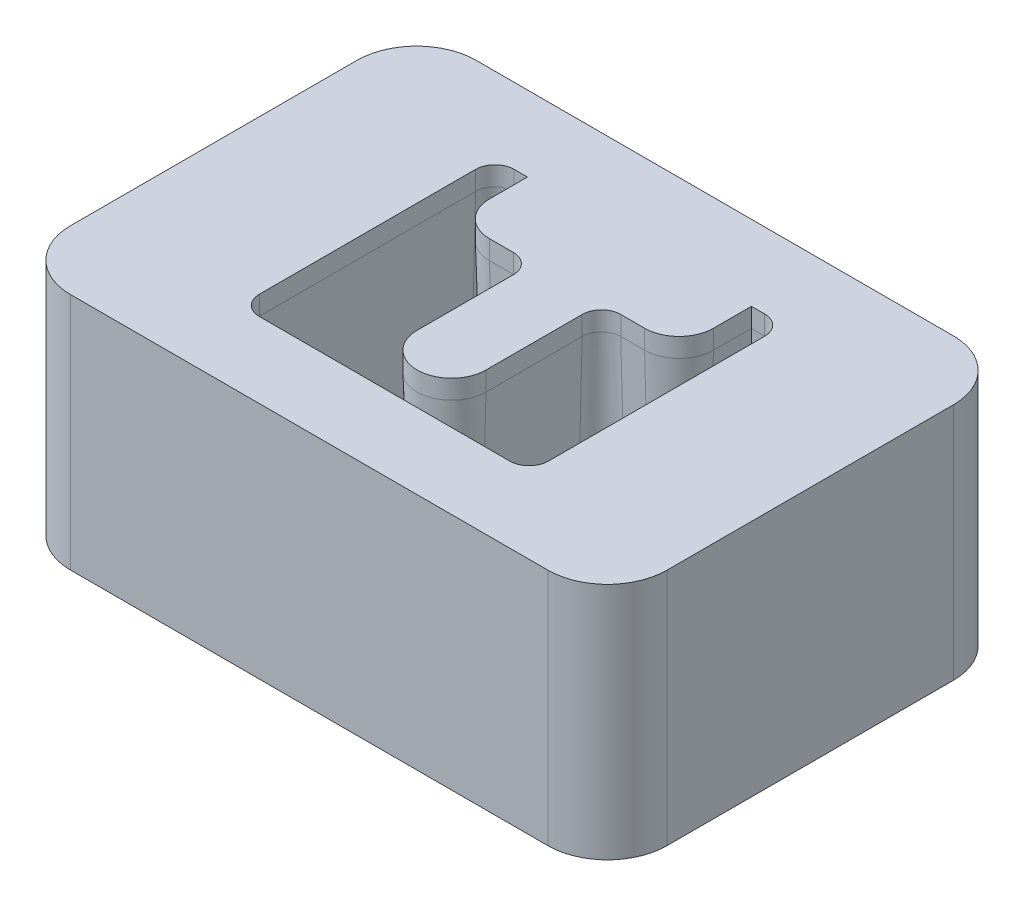
SolidWorks part; units mm, degrees
material "K110"
ref_plane "Front Plane" through (0, 0, 0) normal (0, 0, 1) x (1, 0, 0)
ref_plane "Top Plane" through (0, 0, 0) normal (0, 1, 0) x (1, 0, 0)
ref_plane "Right Plane" through (0, 0, 0) normal (1, 0, 0) x (0, 0, -1)
sketch "Sketch1" plane through (0, 0, 0) normal (0, 1, 0) x (1, 0, 0)
  line L1 (-50, -34) -> (50, -34)
  line L2 (-50, -34) -> (-50, 34)
  line L3 (-50, 34) -> (50, 34)
  line L4 (50, -34) -> (50, 34)
  line L5 (-50, -34) -> (50, 34) construction
  line L6 (-50, 34) -> (50, -34) construction
  point P0 (0, 0)
  dimension "D1" = 68
  dimension "D2" = 100
extrude "Boss-Extrude1" add sketch "Sketch1" against normal blind 40
fillet "Fillet1" radius 10 4 edges at (-50, -20, -34) (50, -20, -34) (50, -20, 34) (-50, -20, 34)
sketch "Sketch2" plane through (0, 0, 0) normal (0, 1, 0) x (1, 0, 0)
  line L22 (-21, -21.36) -> (21, -21.36)
  line L23 (-24.23, 18.13) -> (-24.23, -18.13)
  line L24 (-18.77, 21.36) -> (-21, 21.36)
  line L25 (-18.77, 15) -> (-18.77, 21.36)
  line L26 (-9, 9.23) -> (-13, 9.23)
  line L27 (-5.77, -10.13) -> (-5.77, 6)
  line L28 (5.77, 6) -> (5.77, -10.13)
  line L29 (13, 9.23) -> (9, 9.23)
  line L30 (18.77, 21.36) -> (18.77, 15)
  line L31 (21, 21.36) -> (18.77, 21.36)
  line L32 (24.23, -18.13) -> (24.23, 18.13)
  line L33 (-21, -21.36) -> (21, -21.36)
  line L34 (-24.23, 18.13) -> (-24.23, -18.13)
  line L35 (-18.77, 21.36) -> (-21, 21.36)
  line L36 (-18.77, 15) -> (-18.77, 21.36)
  line L37 (-9, 9.23) -> (-13, 9.23)
  line L38 (-5.77, -10.13) -> (-5.77, 6)
  line L39 (5.77, 6) -> (5.77, -10.13)
  line L40 (13, 9.23) -> (9, 9.23)
  line L41 (18.77, 21.36) -> (18.77, 15)
  line L42 (21, 21.36) -> (18.77, 21.36)
  line L43 (24.23, -18.13) -> (24.23, 18.13)
  arc A18 (21, -21.36) -> (24.23, -18.13) centre (21, -18.13) ccw
  arc A19 (-24.23, -18.13) -> (-21, -21.36) centre (-21, -18.13) ccw
  arc A20 (-21, 21.36) -> (-24.23, 18.13) centre (-21, 18.13) ccw
  arc A21 (-18.77, 15) -> (-13, 9.23) centre (-13, 15) ccw
  arc A22 (-5.77, 6) -> (-9, 9.23) centre (-9, 6) ccw
  arc A23 (-5.77, -10.13) -> (5.77, -10.13) centre (0, -10.13) ccw
  arc A24 (9, 9.23) -> (5.77, 6) centre (9, 6) ccw
  arc A25 (13, 9.23) -> (18.77, 15) centre (13, 15) ccw
  arc A26 (24.23, 18.13) -> (21, 21.36) centre (21, 18.13) ccw
  arc A27 (21, -21.36) -> (24.23, -18.13) centre (21, -18.13) ccw
  arc A28 (-24.23, -18.13) -> (-21, -21.36) centre (-21, -18.13) ccw
  arc A29 (-21, 21.36) -> (-24.23, 18.13) centre (-21, 18.13) ccw
  arc A30 (-18.77, 15) -> (-13, 9.23) centre (-13, 15) ccw
  arc A31 (-5.77, 6) -> (-9, 9.23) centre (-9, 6) ccw
  arc A32 (-5.77, -10.13) -> (5.77, -10.13) centre (0, -10.13) ccw
  arc A33 (9, 9.23) -> (5.77, 6) centre (9, 6) ccw
  arc A34 (13, 9.23) -> (18.77, 15) centre (13, 15) ccw
  arc A35 (24.23, 18.13) -> (21, 21.36) centre (21, 18.13) ccw
  dimension "D1" = 0.23
extrude "Cut-Extrude1" cut sketch "Sketch2" against normal up to next
sketch "Sketch3" plane through (0, 0, 0) normal (0, 0, 1) x (1, 0, 0)
  line L6 (24.23, -3.2) -> (25.1936, -40)
  line L7 (40, -40) -> (40, 0) construction
  line L8 (40, -40) -> (50, -40) construction
  line L11 (37.4031, 0) -> (-37.4031, 0) construction
  line L12 (25.1936, -40) -> (23.23, -40)
  line L13 (-40, -40) -> (40, -40) construction
  line L14 (23.23, -3.2) -> (24.23, -3.2)
  line L15 (23.23, -40) -> (23.23, -3.2)
  line L16 (24.23, -40) -> (24.23, 0) construction
  dimension "D1" = 3.2
  dimension "D2" = 1.5
  dimension "D3" = 1
sketch "Sketch5" plane through (0, 0, 0) normal (0, 1, 0) x (1, 0, 0)
  line L0 (21, 21.36) -> (18.77, 21.36) construction
  line L1 (24.23, -18.13) -> (24.23, 18.13) construction
  line L2 (18.77, 21.36) -> (18.77, 15) construction
  line L3 (13, 9.23) -> (9, 9.23) construction
  line L4 (5.77, 6) -> (5.77, -10.13) construction
  line L5 (-5.77, -10.13) -> (-5.77, 6) construction
  line L6 (-9, 9.23) -> (-13, 9.23) construction
  line L7 (-18.77, 15) -> (-18.77, 21.36) construction
  line L8 (-18.77, 21.36) -> (-21, 21.36) construction
  line L9 (-24.23, 18.13) -> (-24.23, -18.13) construction
  line L10 (-21, -21.36) -> (21, -21.36) construction
  line L11 (-21, -21.36) -> (21, -21.36)
  line L12 (-24.23, 18.13) -> (-24.23, -18.13)
  line L13 (-18.77, 21.36) -> (-21, 21.36)
  line L14 (-18.77, 15) -> (-18.77, 21.36)
  line L15 (-9, 9.23) -> (-13, 9.23)
  line L16 (-5.77, -10.13) -> (-5.77, 6)
  line L17 (5.77, 6) -> (5.77, -10.13)
  line L18 (13, 9.23) -> (9, 9.23)
  line L19 (18.77, 21.36) -> (18.77, 15)
  line L20 (24.23, -18.13) -> (24.23, 18.13)
  line L21 (21, 21.36) -> (18.77, 21.36)
  arc A0 (-5.77, 6) -> (-9, 9.23) centre (-9, 6) ccw construction
  arc A1 (24.23, 18.13) -> (21, 21.36) centre (21, 18.13) ccw construction
  arc A2 (13, 9.23) -> (18.77, 15) centre (13, 15) ccw construction
  arc A3 (9, 9.23) -> (5.77, 6) centre (9, 6) ccw construction
  arc A4 (-5.77, -10.13) -> (5.77, -10.13) centre (0, -10.13) ccw construction
  arc A5 (-18.77, 15) -> (-13, 9.23) centre (-13, 15) ccw construction
  arc A6 (-21, 21.36) -> (-24.23, 18.13) centre (-21, 18.13) ccw construction
  arc A7 (-24.23, -18.13) -> (-21, -21.36) centre (-21, -18.13) ccw construction
  arc A8 (21, -21.36) -> (24.23, -18.13) centre (21, -18.13) ccw construction
  arc A9 (21, -21.36) -> (24.23, -18.13) centre (21, -18.13) ccw
  arc A10 (-24.23, -18.13) -> (-21, -21.36) centre (-21, -18.13) ccw
  arc A11 (-21, 21.36) -> (-24.23, 18.13) centre (-21, 18.13) ccw
  arc A12 (-18.77, 15) -> (-13, 9.23) centre (-13, 15) ccw
  arc A13 (-5.77, 6) -> (-9, 9.23) centre (-9, 6) ccw
  arc A14 (-5.77, -10.13) -> (5.77, -10.13) centre (0, -10.13) ccw
  arc A15 (9, 9.23) -> (5.77, 6) centre (9, 6) ccw
  arc A16 (13, 9.23) -> (18.77, 15) centre (13, 15) ccw
  arc A17 (24.23, 18.13) -> (21, 21.36) centre (21, 18.13) ccw
sweep "Cut-Sweep1" cut profiles "Sketch3" path "Sketch5"
hole_wizard "M6 Tapped Hole1" positions "Sketch11" profile "Sketch9" tap size "M6" standard "ISO"
sketch "Sketch11" plane through (0, -40, 0) normal (0, -1, 0) x (-1, 0, 0)
  line L0 (-40, 34) -> (40, 34) construction
  line L1 (-50, -24) -> (-50, 24) construction
  line L2 (50, 24) -> (50, -24) construction
  line L3 (40, -34) -> (-40, -34) construction
  point P0 (-43, 27)
  point P2 (43, 27)
  point P4 (43, -27)
  point P6 (-43, -27)
  dimension "D1" = 7
  dimension "D2" = 7
  dimension "D3" = 7
  dimension "D4" = 7
sketch "Sketch9" plane through (43, -40, -27) normal (1, 0, 0) x (0, 0, -1)
  line L0 (0, 0) -> (0, 18.5022)
  line L1 (0, 18.5022) -> (2.5, 17)
  line L2 (2.5, 17) -> (2.5, 0.525)
  line L3 (2.5, 0.525) -> (3.025, 0)
  line L5 (3.025, 0) -> (0, 0)
  line L6 (-2.5, 0.525) -> (-3.025, 0) construction
  line L10 (0, 18.5022) -> (-2.5, 17) construction
  line L11 (0, -6.35) -> (0, 107.95) construction
  dimension "Tap Drill Dia." = 5
  dimension "Tap Drill Depth" = 17
  dimension "Near C'Sink Dia." = 6.05
  dimension "Near C'Sink Angle" = 90
  dimension "Drill Angle" = 118
cosmetic thread "Hole Thread1"
cosmetic thread "Hole Thread2"
cosmetic thread "Hole Thread3"
cosmetic thread "Hole Thread4"
